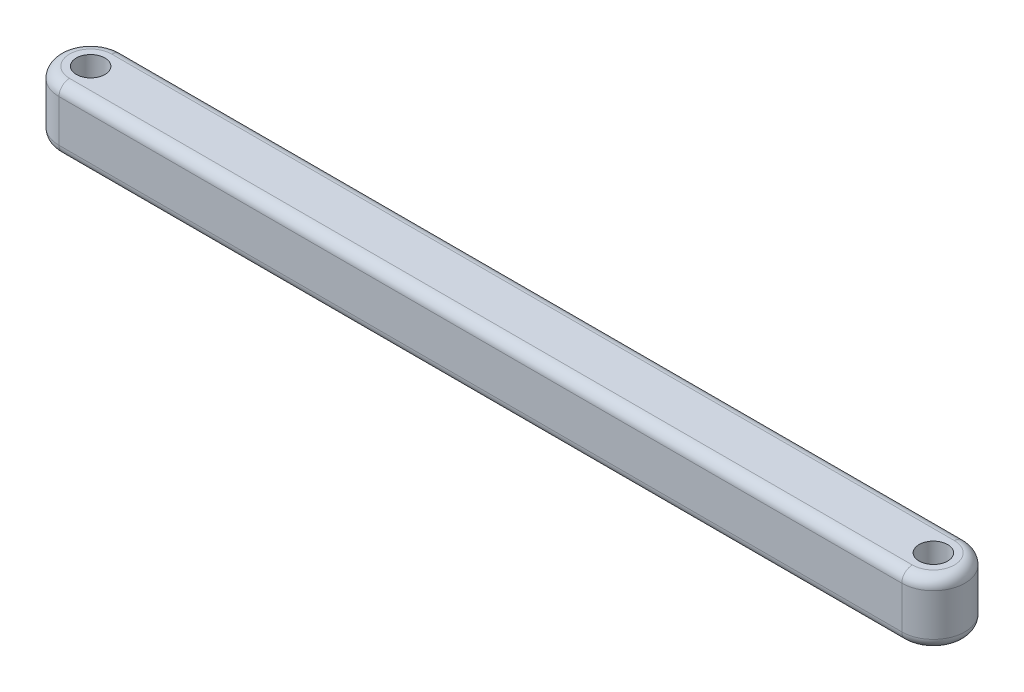
SolidWorks part; units mm, degrees
ref_plane "Front Plane" through (0, 0, 0) normal (0, 0, 1) x (1, 0, 0)
ref_plane "Top Plane" through (0, 0, 0) normal (0, 1, 0) x (1, 0, 0)
ref_plane "Right Plane" through (0, 0, 0) normal (1, 0, 0) x (0, 0, -1)
sketch "Sketch1" plane through (0, 0, 0) normal (0, 1, 0) x (1, 0, 0)
  line L0 (0, 0) -> (127, 0) construction
  line L1 (0, 4.7625) -> (127, 4.7625)
  line L2 (0, -4.7625) -> (127, -4.7625)
  arc A0 (0, 4.7625) -> (0, -4.7625) centre (0, 0) ccw
  arc A1 (127, -4.7625) -> (127, 4.7625) centre (127, 0) ccw
  point P3 (63.5, 0)
  dimension "D1" = 127
  dimension "D2" = 9.525
extrude "Boss-Extrude1" add sketch "Sketch1" along normal mid plane 9.525
sketch "Sketch2" plane through (0, 4.7625, 0) normal (0, 1, 0) x (1, 0, 0)
  circle A0 centre (0, 0) radius 2.159
  circle A1 centre (127, 0) radius 2.159
  dimension "D1" = 4.318
  dimension "D2" = 4.318
extrude "Cut-Extrude1" cut sketch "Sketch2" against normal through all
fillet "Fillet1" radius 1.5875 8 edges at (131.7625, -4.7625, 0) (63.5, -4.7625, 4.7625) (-4.7625, -4.7625, 0) (131.7625, 4.7625, 0) (63.5, 4.7625, 4.7625) (-4.7625, 4.7625, 0) (63.5, -4.7625, -4.7625) (63.5, 4.7625, -4.7625)
